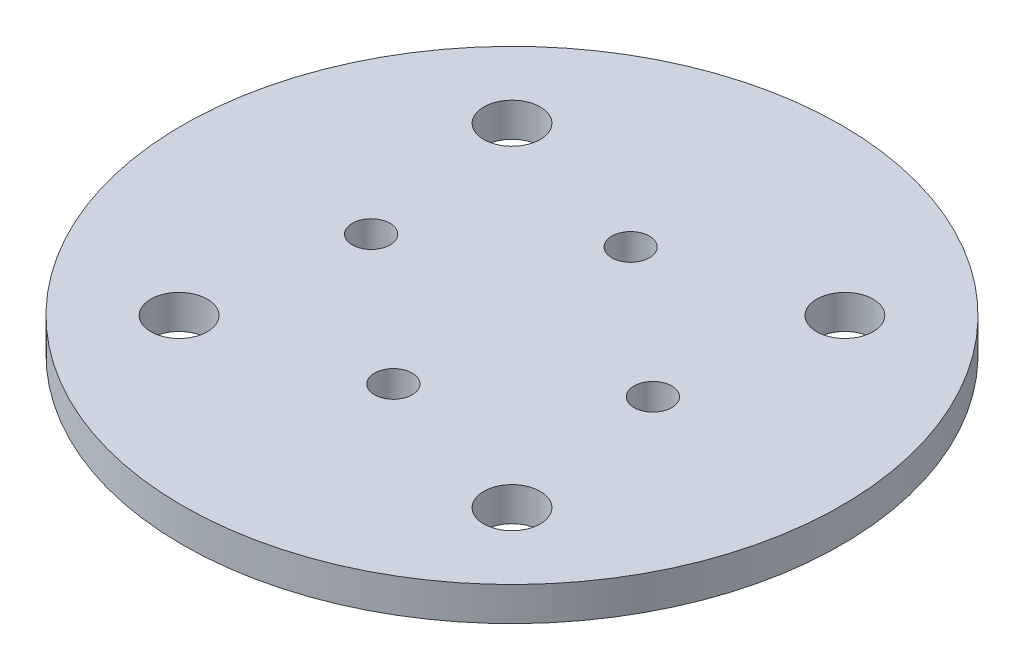
SolidWorks part; units mm, degrees
material "Zoltek Panex 33"
ref_plane "Front Plane" through (0, 0, 0) normal (0, 0, 1) x (1, 0, 0)
ref_plane "Top Plane" through (0, 0, 0) normal (0, 1, 0) x (1, 0, 0)
ref_plane "Right Plane" through (0, 0, 0) normal (1, 0, 0) x (0, 0, -1)
other "Bounding Box"
ref_plane "Default Plane" through (0, 2.286, 19.05) normal (0, -1, 0) x (-1, 0, 0)
sketch "Sketch1" plane through (0, 0, 0) normal (0, 1, 0) x (1, 0, 0)
  line L0 (0, -8) -> (0, 8) construction
  line L1 (-9.5, 0) -> (9.5, 0) construction
  line L2 (-11.2253, -11.2253) -> (11.2253, 11.2253) construction
  line L3 (-11.2253, 11.2253) -> (11.2253, -11.2253) construction
  line L4 (-11.2253, -11.2253) -> (-11.2253, 11.2253) construction
  line L5 (-11.2253, 11.2253) -> (11.2253, 11.2253) construction
  circle A0 centre (0, 0) radius 22.225
  circle A1 centre (0, 8) radius 1.27
  circle A2 centre (9.5, 0) radius 1.27
  circle A3 centre (0, -8) radius 1.27
  circle A4 centre (-9.5, 0) radius 1.27
  circle A5 centre (-11.2253, -11.2253) radius 1.905
  circle A6 centre (11.2253, -11.2253) radius 1.905
  circle A7 centre (11.2253, 11.2253) radius 1.905
  circle A8 centre (-11.2253, 11.2253) radius 1.905
  dimension "D1" = 44.45
  dimension "D2" = 2.54
  dimension "D5" = 3.81
  dimension "D3" = 16
  dimension "D4" = 19
  dimension "D6" = 15.875
extrude "Boss-Extrude1" add sketch "Sketch1" along normal mid plane 2.286
equation "\"Unit Measure\"= \"BoundingVolume\" / \"Thickness\"'in^2"
